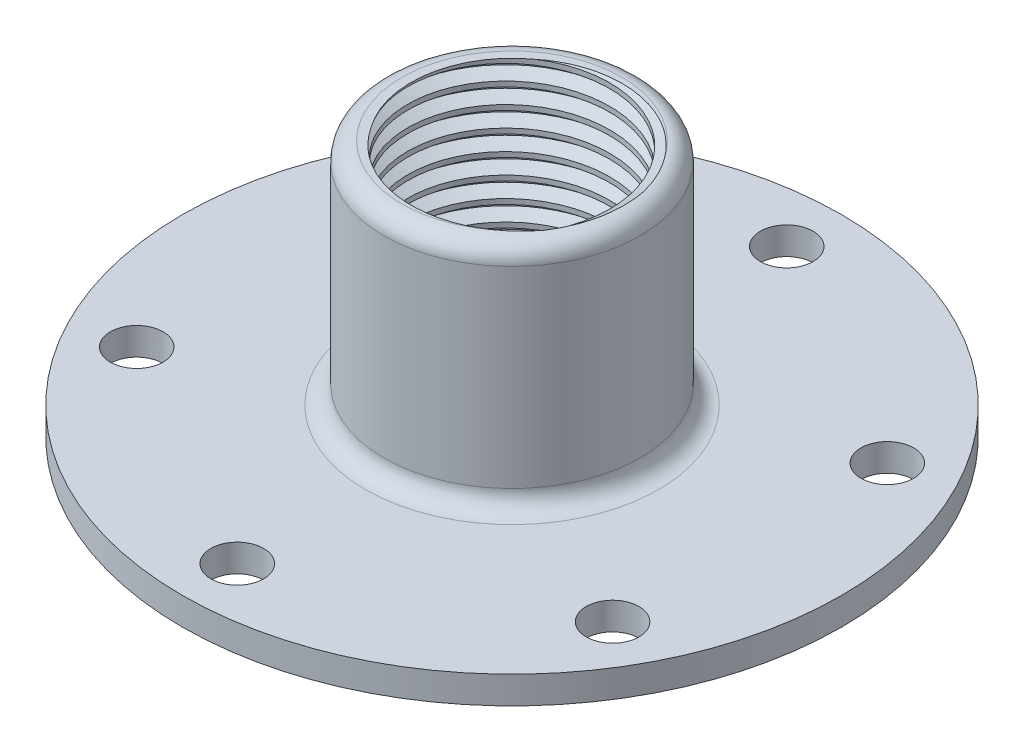
SolidWorks part; units mm, degrees
material "AISI 304"
ref_plane "Front Plane" through (0, 0, 0) normal (0, 0, 1) x (1, 0, 0)
ref_plane "Top Plane" through (0, 0, 0) normal (0, 1, 0) x (1, 0, 0)
ref_plane "Right Plane" through (0, 0, 0) normal (1, 0, 0) x (0, 0, -1)
sketch "Sketch3" plane through (0, 0, 0) normal (0, 0, 1) x (1, 0, 0)
  line L0 (0, 17.78) -> (0, 23.0435) construction
  line L1 (0, 0) -> (22.86, 0)
  line L2 (0, 0) -> (0, 17.78)
  line L3 (8.89, 1.905) -> (22.86, 1.905)
  line L4 (22.86, 0) -> (22.86, 1.905)
  line L5 (0, 0) -> (17.6111, 0)
  line L7 (0, 17.78) -> (8.89, 17.78)
  line L8 (8.89, 1.905) -> (8.89, 17.78)
  dimension "D1" = 1.905
  dimension "D2" = 22.86
  dimension "D3" = 17.78
  dimension "D5" = 8.89
revolve "Revolve1" add sketch "Sketch3" angle 360 about L0 region at (6.0921, 7.7462, 0)
sketch "Sketch4" plane through (0, 17.78, 0) normal (0, 1, 0) x (1, 0, 0)
  circle A0 centre (0, 0) radius 7
extrude "Cut-Extrude1" cut sketch "Sketch4" against normal up to next
thread "Thread1" pitch 1.4111 method cut profile "Thread Profile1" start angle 0, offset 1.27, length 19.05, pitch 1.4111, diameter 14
ref_plane "Plane1" through (-7, 19.05, 0) normal (0, 0, 1) x (-1, 0, 0)
sketch "Thread Profile1" plane through (-7, 19.05, 0) normal (0, 0, 1) x (-1, 0, 0)
  line L0 (0, 0) -> (0, 1.4111) construction
  line L1 (0, 0) -> (0.7638, 0.441)
  line L2 (0.7638, 0.441) -> (0.7638, 0.6174)
  line L3 (0.7638, 0.6174) -> (0, 1.0583)
  line L4 (0.7638, 0.5292) -> (0, 0.5292) construction
  line L11 (0, 0) -> (0, 1.0583)
  point P2 (0, 0)
  dimension "Pitch" = 1.4111
  dimension "Profile_Angle" = 60
  dimension "Profile_Land" = 0.1764
  dimension "Profile_Height" = 0.7638
sketch "Sketch9" plane through (0, 1.905, 0) normal (0, 1, 0) x (1, 0, 0)
  line L0 (0, 0) -> (0, 19.05) construction
  circle A0 centre (0, 19.05) radius 1.8288
  circle A1 centre (16.4978, 9.525) radius 1.8288
  circle A2 centre (16.4978, -9.525) radius 1.8288
  circle A3 centre (0, -19.05) radius 1.8288
  circle A4 centre (-16.4978, -9.525) radius 1.8288
  circle A5 centre (-16.4978, 9.525) radius 1.8288
  point P17 (0, 0)
  dimension "D2" = 6
  dimension "D1" = 19.05
extrude "Cut-Extrude2" cut sketch "Sketch9" against normal up to next
fillet "Fillet1" radius 1.27 2 edges at (0, 1.905, -8.89) (0, 17.78, -8.89)
